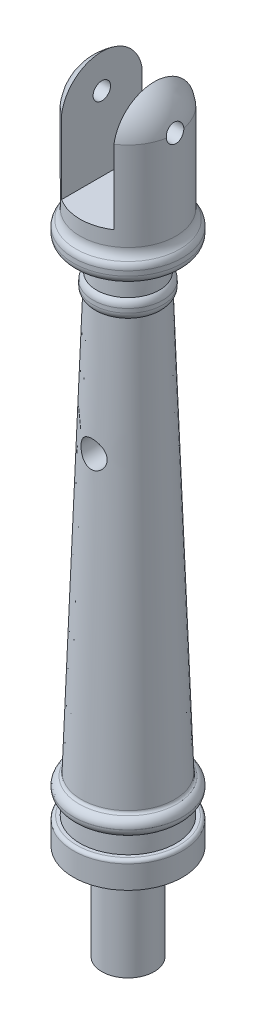
SolidWorks part; units mm, degrees
ref_plane "Front Plane" through (0, 0, 0) normal (0, 0, 1) x (1, 0, 0)
ref_plane "Top Plane" through (0, 0, 0) normal (0, 1, 0) x (1, 0, 0)
ref_plane "Right Plane" through (0, 0, 0) normal (1, 0, 0) x (0, 0, -1)
sketch "Sketch1" plane through (0, 0, 0) normal (0, 0, 1) x (1, 0, 0)
  line L0 (0, 0) -> (0, 114)
  line L1 (0, 114) -> (7, 114)
  line L2 (7, 114) -> (11, 0)
  line L3 (11, 0) -> (0, 0)
  dimension "D1" = 114
  dimension "D2" = 7
  dimension "D3" = 11
revolve "Revolve1" add sketch "Sketch1" angle 360 about L0
sketch "Sketch2" plane through (0, 0, 0) normal (0, -1, 0) x (1, 0, 0)
  circle A0 centre (0, 0) radius 12.5
  dimension "D1" = 25
extrude "Boss-Extrude1" add sketch "Sketch2" along normal blind 6
sketch "Sketch3" plane through (0, -6, 0) normal (0, -1, 0) x (1, 0, 0)
  circle A1 centre (0, 0) radius 12.5
  circle A2 centre (0, 0) radius 12.5
  dimension "D1" = 0
extrude "Boss-Extrude2" add sketch "Sketch3" along normal mid plane 4 from offset 12 offset against normal yes
fillet "Fillet1" radius 2 2 edges at (0, 8, -12.5) (0, 4, -12.5)
fillet "Fillet2" radius 0.75 1 edges at (0, 0, -12.5)
sketch "Sketch4" plane through (0, -6, 0) normal (0, -1, 0) x (1, 0, 0)
  circle A0 centre (0, 0) radius 6
  dimension "D1" = 12
extrude "Boss-Extrude3" add sketch "Sketch4" along normal blind 22
sketch "Sketch5" plane through (0, -28, 0) normal (0, -1, 0) x (1, 0, 0)
  line L0 (-5, 3.3166) -> (-5, -3.3166)
  circle A1 centre (0, 0) radius 6
  arc A2 (-5, 3.3166) -> (-5, -3.3166) centre (0, 0) ccw
  point P5 (-5, 0)
  dimension "D2" = 5
  dimension "D1" = 0
extrude "Cut-Extrude1" cut sketch "Sketch5" against normal blind 15
sketch "Sketch7" plane through (0, 114, 0) normal (0, 1, 0) x (1, 0, 0)
  circle A0 centre (0, 0) radius 8
  dimension "D1" = 16
extrude "Boss-Extrude4" add sketch "Sketch7" along normal mid plane 4 from offset 8 offset against normal yes
fillet "Fillet3" radius 2 2 edges at (0, 104, 8) (0, 108, 8)
sketch "Sketch8" plane through (0, 114, 0) normal (0, 1, 0) x (1, 0, 0)
  circle A0 centre (0, 0) radius 12.5
  dimension "D1" = 25
extrude "Boss-Extrude5" add sketch "Sketch8" along normal blind 5
sketch "Sketch9" plane through (0, 119, 0) normal (0, 1, 0) x (1, 0, 0)
  circle A0 centre (0, 0) radius 11
  dimension "D1" = 22
extrude "Boss-Extrude6" add sketch "Sketch9" along normal blind 22
fillet "Fillet4" radius 2 2 edges at (0, 114, 12.5) (0, 119, 12.5)
fillet "Fillet5" radius 3 1 edges at (0, 119, 11)
fillet "Fillet6" radius 0.75 1 edges at (0, 8, -10.7193)
sketch "Sketch10" plane through (0, 0, 0) normal (0, 0, 1) x (1, 0, 0)
  line L0 (11, 141) -> (0, 141)
  line L1 (11, 141) -> (-11, 141) construction
  line L2 (0, 141) -> (0, 150.5)
  arc A0 (0, 150.5) -> (11, 141) centre (0.1027, 139.5005) cw
  dimension "D2" = 11
  dimension "D1" = 9.5
revolve "Revolve2" add sketch "Sketch10" angle 360 about L2
sketch "Sketch11" plane through (0, 0, 0) normal (0, 0, 1) x (1, 0, 0)
  line L0 (0, 114) -> (0, 158.0871) construction
  line L1 (-7, 114) -> (7, 114) construction
  line L2 (11, 141) -> (-11, 141) construction
  line L3 (6, 152) -> (-6, 152)
  line L4 (6, 152) -> (6, 124)
  line L5 (6, 124) -> (-6, 124)
  line L6 (-6, 152) -> (-6, 124)
  dimension "D1" = 17
  dimension "D2" = 6
  dimension "D3" = 6
  dimension "D4" = 28
extrude "Cut-Extrude2" cut sketch "Sketch11" along normal through all both and the other way through all
sketch "Sketch12" plane through (0, 0, 0) normal (0, 0, 1) x (1, 0, 0)
  line L0 (0, 0) -> (0, 95.9527) construction
  line L1 (-6, -6) -> (6, -6) construction
  circle A0 centre (0, 76) radius 3
  dimension "D2" = 6
  dimension "D1" = 82
extrude "Cut-Extrude3" cut sketch "Sketch12" against normal through all both and the other way through all
sketch "Sketch13" plane through (0, 0, 0) normal (1, 0, 0) x (0, 0, -1)
  line L0 (-9.2195, 141) -> (9.2195, 141) construction
  circle A0 centre (0, 141) radius 2
  dimension "D1" = 4
extrude "Cut-Extrude4" cut sketch "Sketch13" against normal through all both and the other way through all
